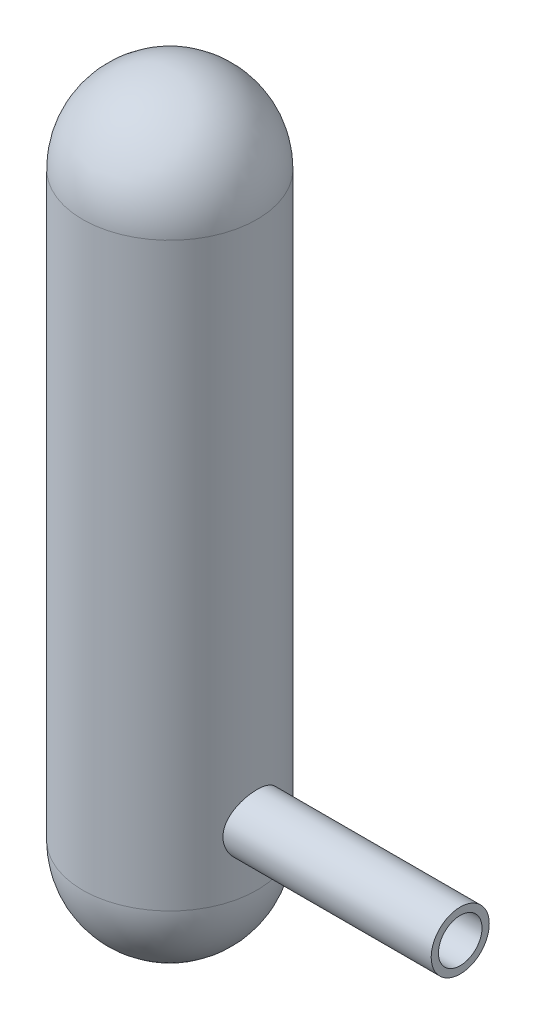
SolidWorks part; units mm, degrees
note: The reader was unsure of these and kept them because the rebuilt part matched: shared geometry of "Sketch4<3>".
ref_plane "Front Plane" through (0, 0, 0) normal (0, 0, 1) x (1, 0, 0)
ref_plane "Top Plane" through (0, 0, 0) normal (0, 1, 0) x (1, 0, 0)
ref_plane "Right Plane" through (0, 0, 0) normal (1, 0, 0) x (0, 0, -1)
sketch "Sketch1" plane through (0, 0, 0) normal (0, 0, 1) x (1, 0, 0)
  line L0 (-250, 0) -> (250, 0) construction
  arc A0 (250, 0) -> (-250, 0) centre (0, 0) ccw
  dimension "D1" = 500
revolve "Revolve-Thin1" add sketch "Sketch1" angle 360 about L0
sketch "Sketch2" plane through (0, 0, 0) normal (0, 0, 1) x (1, 0, 0)
  line L0 (-300, 0) -> (300, 0)
  arc A0 (300, 0) -> (-300, 0) centre (0, 0) ccw
extrude "Cut-Extrude1" cut sketch "Sketch2" against normal mid plane 2000
sketch "Sketch3" plane through (0, 0, 0) normal (0, 1, 0) x (1, 0, 0)
  circle A0 centre (0, 0) radius 300
extrude "Extrude-Thin1" add sketch "Sketch3" along normal blind 2000 thin thin type one direction reverse wall 50
sketch "Sketch4" plane through (0, 0, 0) normal (1, 0, 0) x (0, 0, -1)
  circle A0 centre (0, 200) radius 100
  dimension "D1" = 200
  dimension "D2" = 200
extrude "Cut-Extrude2" cut sketch "Sketch4" along normal blind 5000
extrude "Extrude-Thin2" add sketch "Sketch4<3>" along normal blind 1000 thin thin type one direction reverse wall 25
sketch "Sketch4<3>" plane through (0, 0, 0) normal (1, 0, 0) x (0, 0, -1) same geometry as "Sketch4"
sketch "Sketch7" plane through (0, 0, 0) normal (0, 1, 0) x (1, 0, 0)
  circle A0 centre (0, 0) radius 250
  dimension "D1" = 500
extrude "Cut-Extrude3" cut sketch "Sketch7" along normal blind 500
sketch "Sketch5" plane through (1000, 0, 0) normal (1, 0, 0) x (0, 0, -1)
  circle A0 centre (0, 200) radius 75
  circle A1 centre (0, 200) radius 100
  dimension "D1" = 200
  dimension "D2" = 150
sketch "Sketch8" plane through (0, 2000, 0) normal (0, 1, 0) x (1, 0, 0)
  line L0 (-300, 0) -> (300, 0)
  circle A0 centre (0, 0) radius 300 construction
  arc A1 (282.8427, -100) -> (282.8427, 100) centre (0, 0) ccw construction
  arc A2 (300, 0) -> (-300, 0) centre (0, 0) ccw
  dimension "D1" = 600
revolve "Revolve2" add sketch "Sketch8" angle 180 about L0
